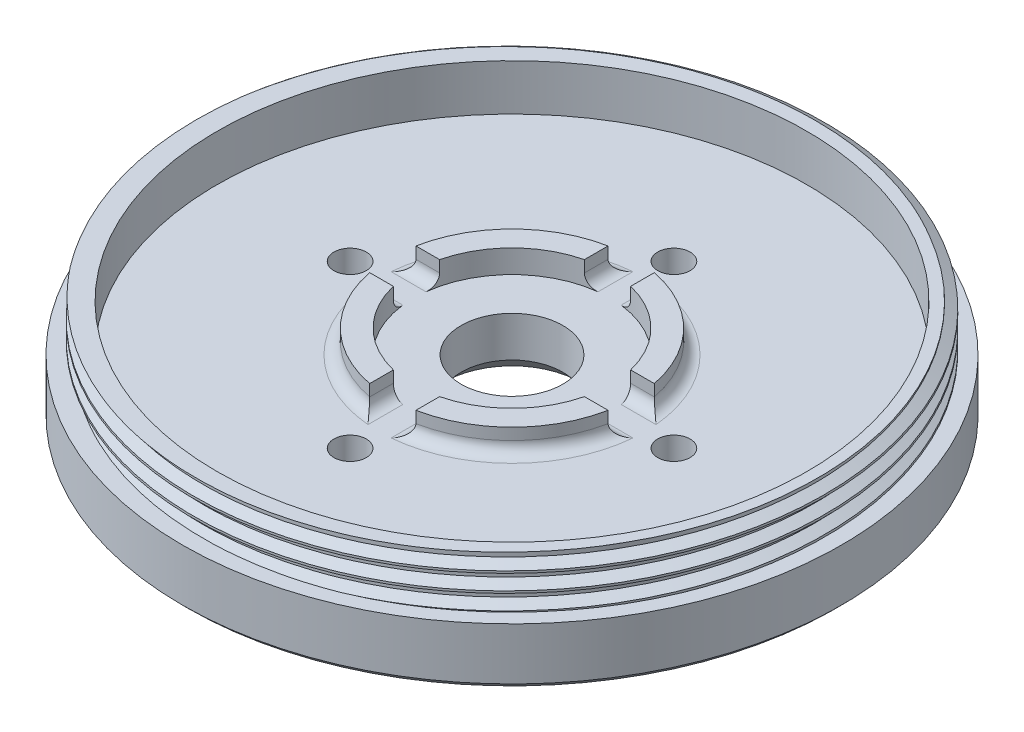
SolidWorks part; units mm, degrees
ref_plane "Front plane" through (0, 0, 0) normal (0, 0, 1) x (1, 0, 0)
ref_plane "Top plane" through (0, 0, 0) normal (0, 1, 0) x (1, 0, 0)
ref_plane "Right plane" through (0, 0, 0) normal (1, 0, 0) x (0, 0, -1)
ref_axis "Axis X" through (0, 0, 0) along (1, 0, 0)
ref_axis "Axis Y" through (0, 0, 0) along (0, 1, 0)
ref_axis "Axis Z" through (0, 0, 0) along (0, 0, 1)
sketch "Sketch1" plane through (0, 0, 0) normal (0, 1, 0) x (1, 0, 0)
  circle A0 centre (0, 0) radius 28.5
  circle A1 centre (0, 0) radius 4.4
  circle A2 centre (0, 0) radius 14 construction
  circle A3 centre (0, 14) radius 1.4
  circle A4 centre (14, 0) radius 1.4
  circle A5 centre (0, -14) radius 1.4
  circle A6 centre (-14, 0) radius 1.4
  point P16 (0, 0)
  dimension "D1" = 57
  dimension "D2" = 8.8
  dimension "D3" = 28
  dimension "D4" = 2.8
  dimension "D5" = 4
extrude "Extrude1" add sketch "Sketch1" along normal blind 5
sketch "Sketch8" plane through (0, 5, 0) normal (0, 1, 0) x (1, 0, 0)
  circle A1 centre (0, 0) radius 25.5
  circle A3 centre (0, 0) radius 26.45
  dimension "D1" = 51
  dimension "D2" = 0.95
extrude "Бобышка-Вытянуть1" add sketch "Sketch8" along normal blind 4
thread "Резьба1" pitch 1.5 method extrude trim with start face yes trim with end face yes profile "Профиль резьбы1" start angle 0, offset 2, length 0, pitch 1.5, diameter 52.9
ref_plane "Плоскость1" through (-26.45, 11, 0) normal (0, 0, 1) x (-1, 0, 0)
sketch "Профиль резьбы1" plane through (-26.45, 11, 0) normal (0, 0, 1) x (-1, 0, 0)
  line L0 (0, 0) -> (0, 1.5) construction
  line L1 (0, 0) -> (0.8119, 0.4687)
  line L2 (0.8119, 0.4687) -> (0.8119, 0.6562)
  line L3 (0.8119, 0.6562) -> (0, 1.125)
  line L4 (0.8119, 0.5625) -> (0, 0.5625) construction
  line L11 (0, 0) -> (0, 1.125)
  point P2 (0, 0)
  dimension "Pitch" = 1.5
  dimension "Profile_Angle" = 60
  dimension "Profile_Land" = 0.1875
  dimension "Profile_Height" = 0.8119
sketch "Эскиз3" plane through (0, 5, 0) normal (0, 1, 0) x (1, 0, 0)
  line L0 (0, 0) -> (0, 10) construction
  line L1 (-2, 10.3078) -> (-2, 8.2614)
  line L2 (2, 10.3078) -> (2, 8.2614)
  line L3 (10.3078, 2) -> (8.2614, 2)
  line L4 (10.3078, -2) -> (8.2614, -2)
  line L5 (2, -10.3078) -> (2, -8.2614)
  line L6 (-2, -10.3078) -> (-2, -8.2614)
  line L7 (-10.3078, -2) -> (-8.2614, -2)
  line L8 (-10.3078, 2) -> (-8.2614, 2)
  arc A0 (-2, 8.2614) -> (-8.2614, 2) centre (0, 0) ccw
  arc A1 (-2, 10.3078) -> (-10.3078, 2) centre (0, 0) ccw
  arc A2 (8.2614, 2) -> (2, 8.2614) centre (0, 0) ccw
  arc A3 (10.3078, 2) -> (2, 10.3078) centre (0, 0) ccw
  arc A4 (-8.2614, -2) -> (-2, -8.2614) centre (0, 0) ccw
  arc A5 (-10.3078, -2) -> (-2, -10.3078) centre (0, 0) ccw
  arc A6 (2, -8.2614) -> (8.2614, -2) centre (0, 0) ccw
  arc A7 (2, -10.3078) -> (10.3078, -2) centre (0, 0) ccw
  dimension "D1" = 17
  dimension "D2" = 2
  dimension "D3" = 4
  dimension "D4" = 4
extrude "Бобышка-Вытянуть2" add sketch "Эскиз3" along normal blind 2
fillet "Скругление1" radius 1 12 edges at (-2, 5, -9.2846) (2, 5, -9.2846) (7.4246, 5, -7.4246) (9.2846, 5, -2) (9.2846, 5, 2) (7.4246, 5, 7.4246) (-7.4246, 5, -7.4246) (-7.4246, 5, 7.4246) (2, 5, 9.2846) (-2, 5, 9.2846) (-9.2846, 5, 2) (-9.2846, 5, -2)
chamfer "Chamfer2" distance 1.5 angle 45 1 edges at (0, 0, 4.4)
chamfer "Chamfer3" distance 0.5 angle 45 1 edges at (0, 0, 28.5)
chamfer "Chamfer4" distance 1 angle 45 4 edges at (0, 0, -12.6) (14, 0, 1.4) (-14, 0, 1.4) (0, 0, 15.4)
equation "\"motor_D\"= 49'Motor diameter"
equation "\"motor_H\"= 19'Motor heigh"
equation "\"motor_d1\"= 38.5'Seating diameter of screws on the fixed part of the motor"
equation "\"motor_s1\"= 2.5'Screws diameter on the fixed part of motor"
equation "\"motor_a2\"= 0'Seating parameter in rectangle of screws on the moving part of the motor"
equation "\"motor_s2\"= 3'Screws diameter on the moving part of motor"
equation "\"motor_Dc\"= 5'Central hole diameter of motor"
equation "\"bearing_d1\"= 6'Bearing inner diameter"
equation "\"bearing_d2\"= 17'Bearing external diameter"
equation "\"bearing h\"= 6'Bearing heigh"
equation "\"pin_d\"= 2'Pin diameter"
equation "\"pin_h\"= 13'Pin heigh"
equation "\"magnet_d1\"= 5'Magnet inner diameter"
equation "\"magnet_d2\"= 9.5'Magnet external diameter"
equation "\"magnet_h\"= 3'Magnet heigh"
equation "\"motor_b2\"= 0'Seating parameter in rectangle of screws on the moving part of the motor"
equation "\"motor_d2\"= 25'Seating diameter of screws on the moving part of the motor (if this parameter is not determine, write 0)"
equation "\"motor_cmd\"= 17'Central magnet mount diameter"
equation "\"motor_cmh\"= 1'Central magnet mount heigh (if not write 0)"
equation "\"motor_whR\"= 17'Distance from center of motor to wires"
equation "\"D1@Sketch1\"= IIF ( \"motor_D\" < 34 , 41 , \"motor_D\" + 8 )"
equation "\"D2@Sketch1\"=\"ft_sensor_d1\"-1"
equation "\"D4@Sketch1\"=3-\"print_offset\""
equation "\"print_offset\"= 0.2'Offset for printing holes"
equation "\"ft_sensor_d1\"= 9.8"
equation "\"ft_sensor_d2\"= 24.9"
equation "\"ft_sensor_d3\"= 22.6'Inner diameter of "
equation "\"ft_sensor_h\"= 7.1"
equation "\"ft_sensor_whD\" = 5"
equation "\"D1@Sketch8\" = IIF ( \"motor_D\" < 34 , 41 , \"motor_D\" + 8 ) - 6"
equation "\"D2@Sketch8\"= 0.95"
equation "\"D1@Эскиз3\"=\"bearing_d2\""
equation "\"D1@Бобышка-Вытянуть2\"=\"bearing h\"/3"
